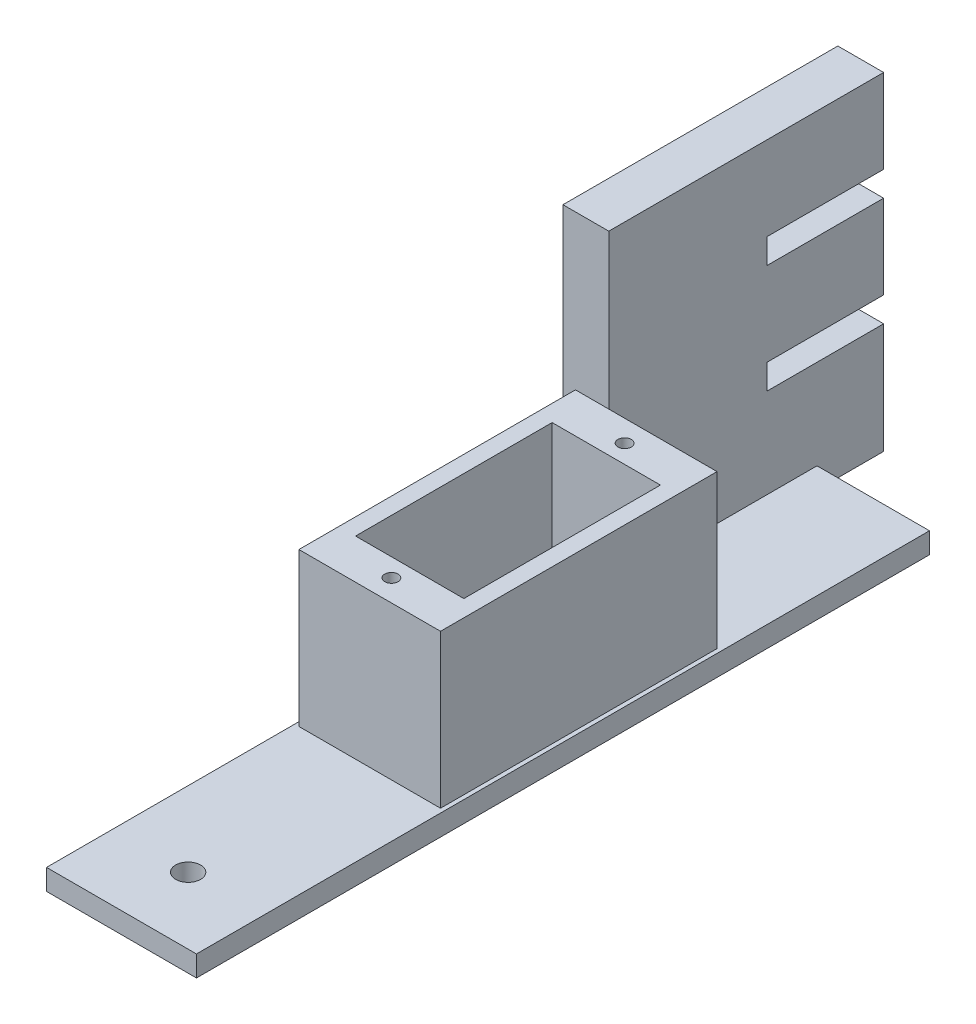
SolidWorks part; units mm, degrees
ref_plane "Front Plane" through (0, 0, 0) normal (0, 0, 1) x (1, 0, 0)
ref_plane "Top Plane" through (0, 0, 0) normal (0, 1, 0) x (1, 0, 0)
ref_plane "Right Plane" through (0, 0, 0) normal (1, 0, 0) x (0, 0, -1)
ref_plane "PZ_m80_000" through (0, 0, -80) normal (0, 0, 1) x (1, 0, 0)
sketch "S_box1" plane through (0, 0, -80) normal (0, 0, 1) x (1, 0, 0)
  line L0 (-9, -20.7) -> (9, -20.7)
  line L1 (9, -20.7) -> (9, -18.2)
  line L2 (9, -18.2) -> (-9, -18.2)
  line L3 (-9, -18.2) -> (-9, -20.7)
  dimension "P1" = 9
  dimension "P2" = 20.7
  dimension "P3" = 9
  dimension "P4" = 20.7
  dimension "P5" = 9
  dimension "P6" = 18.2
  dimension "P7" = 9
  dimension "P8" = 18.2
extrude "Boss_1" add sketch "S_box1" along normal blind 88
ref_plane "PZ_m55_000" through (0, 0, -55) normal (0, 0, 1) x (1, 0, 0)
sketch "S_box2" plane through (0, 0, -55) normal (0, 0, 1) x (1, 0, 0)
  line L0 (-8.5, -18.2) -> (8.5, -18.2)
  line L1 (8.5, -18.2) -> (8.5, 0.2)
  line L2 (8.5, 0.2) -> (-8.5, 0.2)
  line L3 (-8.5, 0.2) -> (-8.5, -18.2)
  dimension "P1" = 8.5
  dimension "P2" = 18.2
  dimension "P3" = 8.5
  dimension "P4" = 18.2
  dimension "P5" = 8.5
  dimension "P6" = 0.2
  dimension "P7" = 8.5
  dimension "P8" = 0.2
extrude "Boss_2" add sketch "S_box2" along normal blind 33.2
ref_plane "PZ_m88_000" through (0, 0, -88) normal (0, 0, 1) x (1, 0, 0)
sketch "S_box3" plane through (0, 0, -88) normal (0, 0, 1) x (1, 0, 0)
  line L0 (-10, -20.7) -> (-4.5, -20.7)
  line L1 (-4.5, -20.7) -> (-4.5, 18.7)
  line L2 (-4.5, 18.7) -> (-10, 18.7)
  line L3 (-10, 18.7) -> (-10, -20.7)
  dimension "P1" = 10
  dimension "P2" = 20.7
  dimension "P3" = 4.5
  dimension "P4" = 20.7
  dimension "P5" = 4.5
  dimension "P6" = 18.7
  dimension "P7" = 10
  dimension "P8" = 18.7
extrude "Boss_3" add sketch "S_box3" along normal blind 33
ref_plane "PZ_m50_200" through (0, 0, -50.2) normal (0, 0, 1) x (1, 0, 0)
sketch "S_cut4" plane through (0, 0, -50.2) normal (0, 0, 1) x (1, 0, 0)
  line L0 (-6.5, -18.2) -> (6.5, -18.2)
  line L1 (6.5, -18.2) -> (6.5, 0.3)
  line L2 (6.5, 0.3) -> (-6.5, 0.3)
  line L3 (-6.5, 0.3) -> (-6.5, -18.2)
  dimension "P1" = 6.5
  dimension "P2" = 18.2
  dimension "P3" = 6.5
  dimension "P4" = 18.2
  dimension "P5" = 6.5
  dimension "P6" = 0.3
  dimension "P7" = 6.5
  dimension "P8" = 0.3
extrude "Pocket_4" cut sketch "S_cut4" along normal blind 23.6
ref_plane "PY_m20_800" through (0, -20.8, 0) normal (0, 1, 0) x (1, 0, 0)
sketch "S_hole5" plane through (0, -20.8, 0) normal (0, 1, 0) x (1, 0, 0)
  circle A0 centre (0, 0) radius 1.5
  dimension "D1_S_hole5" = 3
extrude "Hole_5" cut sketch "S_hole5" along normal blind 2.7
ref_plane "PY_m5_800" through (0, -5.8, 0) normal (0, 1, 0) x (1, 0, 0)
sketch "S_hole6" plane through (0, -5.8, 0) normal (0, 1, 0) x (1, 0, 0)
  circle A0 centre (0, 52.4) radius 0.8
  dimension "D1_S_hole6" = 1.6
  dimension "P2" = 52.4
extrude "Hole_6" cut sketch "S_hole6" along normal blind 6.1
sketch "S_hole7" plane through (0, -5.8, 0) normal (0, 1, 0) x (1, 0, 0)
  circle A0 centre (0, 24.4) radius 0.8
  dimension "D1_S_hole7" = 1.6
  dimension "P2" = 24.4
extrude "Hole_7" cut sketch "S_hole7" along normal blind 6.1
ref_plane "PZ_m88_100" through (0, 0, -88.1) normal (0, 0, 1) x (1, 0, 0)
sketch "S_cut8" plane through (0, 0, -88.1) normal (0, 0, 1) x (1, 0, 0)
  line L0 (-10.1, 5.63) -> (-4.4, 5.63)
  line L1 (-4.4, 5.63) -> (-4.4, 8.63)
  line L2 (-4.4, 8.63) -> (-10.1, 8.63)
  line L3 (-10.1, 8.63) -> (-10.1, 5.63)
  dimension "P1" = 10.1
  dimension "P2" = 5.63
  dimension "P3" = 4.4
  dimension "P4" = 5.63
  dimension "P5" = 4.4
  dimension "P6" = 8.63
  dimension "P7" = 10.1
  dimension "P8" = 8.63
extrude "Pocket_8" cut sketch "S_cut8" along normal blind 14.1
sketch "S_cut9" plane through (0, 0, -88.1) normal (0, 0, 1) x (1, 0, 0)
  line L0 (-10.1, -7.43) -> (-4.4, -7.43)
  line L1 (-4.4, -7.43) -> (-4.4, -4.43)
  line L2 (-4.4, -4.43) -> (-10.1, -4.43)
  line L3 (-10.1, -4.43) -> (-10.1, -7.43)
  dimension "P1" = 10.1
  dimension "P2" = 7.43
  dimension "P3" = 4.4
  dimension "P4" = 7.43
  dimension "P5" = 4.4
  dimension "P6" = 4.43
  dimension "P7" = 10.1
  dimension "P8" = 4.43
extrude "Pocket_9" cut sketch "S_cut9" along normal blind 14.1
equation "\"plate_t\" = 3"
equation "\"clearance\" = 0.4"
